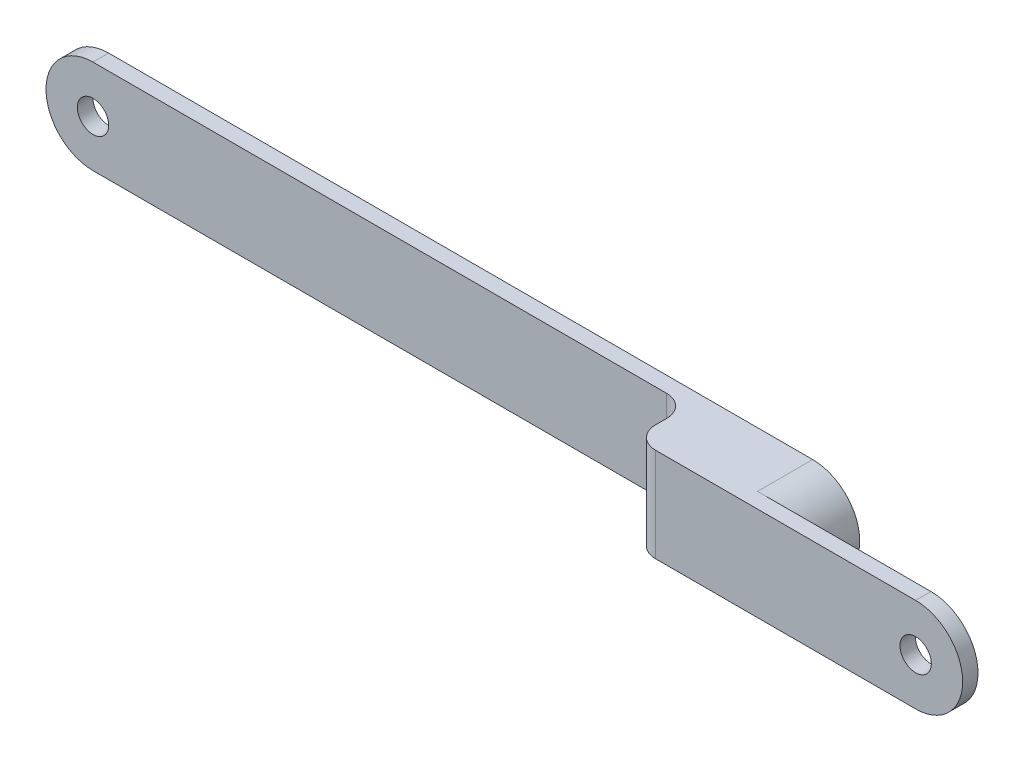
SolidWorks part; units mm, degrees
ref_plane "Front Plane" through (0, 0, 0) normal (0, 0, 1) x (1, 0, 0)
ref_plane "Top Plane" through (0, 0, 0) normal (0, 1, 0) x (1, 0, 0)
ref_plane "Right Plane" through (0, 0, 0) normal (1, 0, 0) x (0, 0, -1)
sketch "Sketch1" plane through (0, 0, 0) normal (0, 0, 1) x (1, 0, 0)
  line L0 (0, 0) -> (200, 0) construction
  line L1 (0, 15) -> (200, 15)
  line L2 (0, -15) -> (200, -15)
  arc A0 (0, 15) -> (0, -15) centre (0, 0) ccw
  arc A1 (200, -15) -> (200, 15) centre (200, 0) ccw
  point P3 (100, 0)
  dimension "D1" = 30
  dimension "D2" = 200
extrude "Boss-Extrude1" add sketch "Sketch1" along normal blind 45
sketch "Sketch2" plane through (0, 0, 45) normal (0, 0, 1) x (1, 0, 0)
  circle A0 centre (0, 0) radius 5
  dimension "D1" = 10
extrude "Cut-Extrude1" cut sketch "Sketch2" against normal blind 90
sketch "Sketch6" plane through (0, 0, 0) normal (0, 0, -1) x (-1, 0, 0)
sketch "Sketch7" plane through (0, -15, 0) normal (0, -1, 0) x (1, 0, 0)
  line L0 (215, 22.5) -> (190, 22.5)
  line L1 (215, 0) -> (215, 45) construction
  line L2 (190, 22.5) -> (190, 5)
  line L3 (190, 5) -> (-15, 5)
  line L4 (-15, 45) -> (-15, 0) construction
  line L5 (-15, 5) -> (-15, 0)
  line L6 (-15, 0) -> (215, 0)
  line L7 (215, 0) -> (215, 22.5)
  dimension "D1" = 5
  dimension "D2" = 25
extrude "Cut-Extrude2" cut sketch "Sketch7" against normal blind 50 flip side to cut
fillet "Fillet1" radius 7 2 edges at (190, 0, 22.5) (190, 0, 5)
sketch "Sketch8" plane through (0, 0, 22.5) normal (0, 0, 1) x (1, 0, 0)
  line L0 (200, 15) -> (280, 15)
  line L1 (280, -15) -> (200, -15)
  line L3 (200, 15) -> (200, -15)
  arc A0 (280, 15) -> (280, -15) centre (280, 0) cw
  dimension "D1" = 280
extrude "Boss-Extrude2" add sketch "Sketch8" along direction (0, 0, 1) on the side against the normal up to surface (22.5 mm away) up to face at (5, 0, 0)
sketch "Sketch10" plane through (0, 0, 0) normal (0, 0, -1) x (-1, 0, 0)
  circle A0 centre (-280, 0) radius 15
  arc A1 (-280, 15) -> (-280, -15) centre (-280, 0) ccw construction
extrude "Cut-Extrude3" cut sketch "Sketch10" against normal blind 17.6
fillet "Fillet3" radius 7 2 edges at (280, -15, 8.8) (280, 15, 8.8)
sketch "Sketch11" plane through (0, 0, 0) normal (0, 0, -1) x (-1, 0, 0)
  line L0 (0, -15) -> (-259.5061, -15) construction
  line L1 (-259.5061, 15) -> (0, 15) construction
  line L2 (-224.6454, -15) -> (-269.753, -15)
  line L3 (-259.5061, -15) -> (-280, -15) construction
  line L4 (-269.753, -15) -> (-269.753, 15)
  line L5 (-280, 15) -> (-259.5061, 15) construction
  line L6 (-269.753, 15) -> (-224.6454, 15)
  arc A0 (-224.6454, -15) -> (-224.6454, 15) centre (-224.6454, 0) cw
  point P3 (-230.2503, 15)
  point P14 (0, 0)
  point P15 (-235.3649, 15)
extrude "Cut-Extrude4" cut sketch "Sketch11" against normal up to surface (17.6 mm away) up to face at (271.6797, 0, 17.6)
sketch "Sketch12" plane through (0, 0, 17.6) normal (0, 0, -1) x (-1, 0, 0)
  circle A0 centre (-280, 0) radius 5
  circle A2 centre (0, 0) radius 5 construction
extrude "Cut-Extrude5" cut sketch "Sketch12" against normal blind 15
